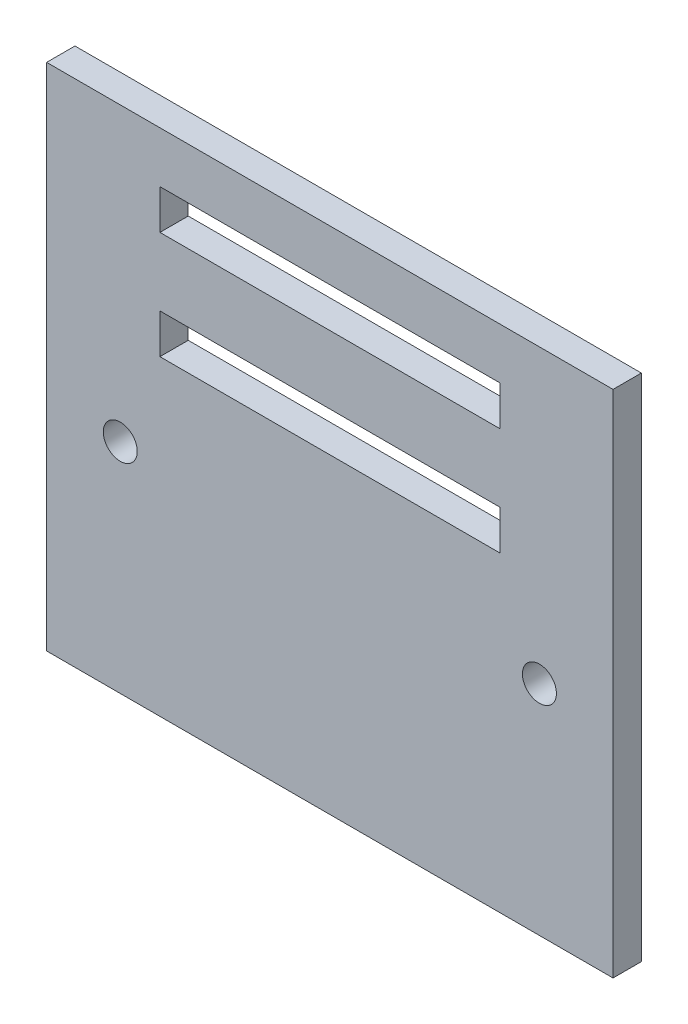
SolidWorks part; units mm, degrees
material "PBT General Purpose"
ref_plane "Front Plane" through (0, 0, 0) normal (0, 0, 1) x (1, 0, 0)
ref_plane "Top Plane" through (0, 0, 0) normal (0, 1, 0) x (1, 0, 0)
ref_plane "Right Plane" through (0, 0, 0) normal (1, 0, 0) x (0, 0, -1)
sketch "frame_outline" plane through (0, 0, 0) normal (0, 0, 1) x (1, 0, 0)
  line L123 (0.65, 1.925) -> (4.35, 1.925) construction
  line L124 (0, 0) -> (5, 0)
  line L125 (0, 0) -> (0, 4.5)
  line L126 (0, 4.5) -> (5, 4.5)
  line L127 (5, 0) -> (5, 4.5)
  line L132 (1, 3.1) -> (4, 3.1)
  line L133 (1, 3.1) -> (1, 2.75)
  line L134 (1, 2.75) -> (4, 2.75)
  line L135 (4, 3.1) -> (4, 2.75)
  line L136 (1, 3.7) -> (4, 3.7)
  line L137 (1, 3.7) -> (1, 4.05)
  line L138 (1, 4.05) -> (4, 4.05)
  line L139 (4, 3.7) -> (4, 4.05)
  circle A0 centre (0.65, 1.925) radius 0.15
  circle A1 centre (4.35, 1.925) radius 0.15
  point P12 (2.5, 2.75)
  point P13 (2.5, 0)
  point P18 (2.5, 1.925)
  point P19 (1, 2.925)
  dimension "D7" = 0.3
  dimension "D8" = 0.3
  dimension "D1" = 3
  dimension "D2" = 5
  dimension "D3" = 0.35
  dimension "D4" = 4.5
  dimension "D5" = 2.75
  dimension "D6" = 3.7
  dimension "D9" = 1.85
  dimension "D10" = 1
extrude "Boss-Extrude1" add sketch "frame_outline" along normal mid plane 0.25
equation "\"t\"= 0.25'thickness of the sheets"
equation "\"t_cf\" = 0.115'thickness of single carbon fiber layer"
equation "\"t_kapton\" = 0.025'thickness of single Kapton flex layer"
equation "\"t_fr4\" = 0.1'thickness of FR4 with copper layer"
equation "\"joint_flex\"= 0.1'Width of flextures gap"
equation "\"joint_flex_eff\"= 0.02'Width of flecture after castelation"
equation "\"joint_fold\"= 0.2'Width of folding joints for 90deg fold"
equation "\"gap_tolerance\"= 0.002'Width to have interfecence fit between carbon fiber inserts"
equation "\"assemble_angle\"= 90'Angle of assembly parts"
equation "\"D1@Boss-Extrude1\"=\"t\""
equation "\"link_lift\"= 0.5'Actuation linkage amplification for the lift motion"
equation "\"link_swing\"= 0.45'Actuation linkage amplification for the swing motion"
equation "\"D3@frame_outline\"=0.35"
